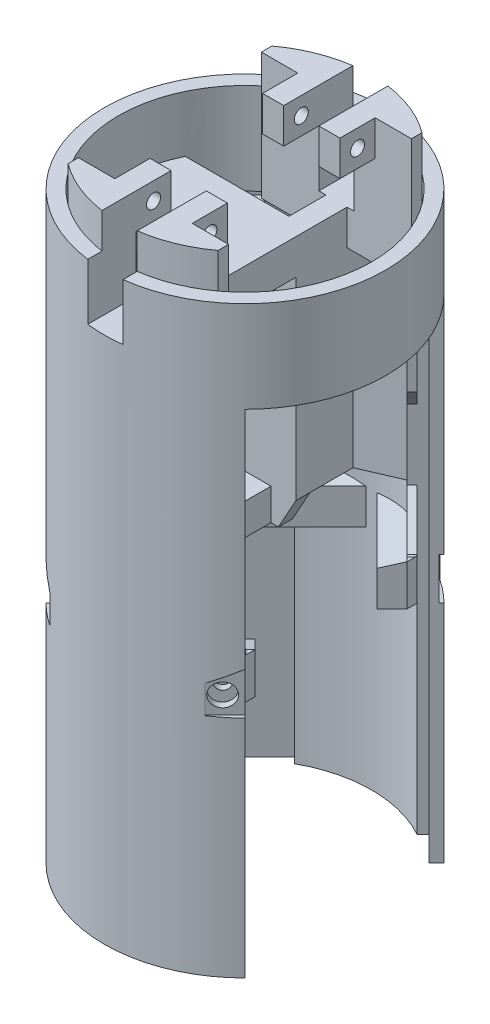
SolidWorks part; units mm, degrees
ref_plane "前视基准面" through (0, 0, 0) normal (0, 0, 1) x (1, 0, 0)
ref_plane "上视基准面" through (0, 0, 0) normal (0, 1, 0) x (1, 0, 0)
ref_plane "右视基准面" through (0, 0, 0) normal (1, 0, 0) x (0, 0, -1)
other "Configuration Table"
sketch "草图1" plane through (0, 0, 0) normal (0, 1, 0) x (1, 0, 0)
  circle A0 centre (0, 0) radius 20
  circle A1 centre (0, 0) radius 18
  dimension "D1" = 40
  dimension "D2" = 36
extrude "凸台-拉伸1" add sketch "草图1" along normal blind 5
sketch "草图2" plane through (0, 0, 0) normal (0, 1, 0) x (1, 0, 0)
  line L0 (0, -1000) -> (0, 49000) construction
  line L2 (-1.5, 17.9374) -> (-1.5, -17.9374)
  line L3 (1.5, 17.9374) -> (1.5, -17.9374)
  arc A0 (-1.5, -17.9374) -> (1.5, -17.9374) centre (0, 0) ccw
  arc A1 (1.5, 17.9374) -> (-1.5, 17.9374) centre (0, 0) ccw
  point P7 (0, 17.9374)
  dimension "D1" = 36
  dimension "D2" = 3
  dimension "D3" = 35.8748
extrude "凸台-拉伸2" add sketch "草图2" along normal blind 5
sketch "草图14" plane through (0, 0, 0) normal (0, 1, 0) x (1, 0, 0)
  line L0 (-1000, 0) -> (49000, 0) construction
  line L1 (0, -1000) -> (0, 49000) construction
  line L2 (-12.4499, 13) -> (12.4499, 13)
  line L3 (-1000, 18) -> (49000, 18) construction
  line L4 (-12.4499, -13) -> (12.4499, -13)
  arc A0 (-12.4499, -13) -> (12.4499, -13) centre (0, 0) ccw
  arc A1 (12.4499, 13) -> (-12.4499, 13) centre (0, 0) ccw
  point P11 (0, 13)
  dimension "D1" = 5
extrude "凸台-拉伸8" add sketch "草图14" along normal up to surface (5 mm away) up to face at (-9.75, 5, 0)
sketch "草图17" plane through (0, 0, 0) normal (0, 1, 0) x (1, 0, 0)
  line L0 (12.4499, 13) -> (2.5, 13)
  line L1 (-1000, 0) -> (49000, 0) construction
  line L12 (-2.5, 13) -> (-12.4499, 13)
  line L26 (-2.5, 17.8255) -> (-2.5, 13)
  line L27 (2.5, 17.8255) -> (2.5, 13)
  line L28 (2.5, -17.8255) -> (2.5, -13)
  line L29 (-2.5, -17.8255) -> (-2.5, -13)
  line L30 (-2.5, -13) -> (-12.4499, -13)
  line L31 (12.4499, -13) -> (2.5, -13)
  arc A0 (-2.5, 17.8255) -> (-12.4499, 13) centre (0, 0) ccw
  arc A1 (12.4499, 13) -> (2.5, 17.8255) centre (0, 0) ccw
  arc A4 (12.4499, -13) -> (2.5, -17.8255) centre (0, 0) cw
  arc A5 (-2.5, -17.8255) -> (-12.4499, -13) centre (0, 0) cw
  dimension "D1" = 4.8255
  dimension "D2" = 5
extrude "凸台-拉伸10" add sketch "草图17" along normal blind 13 from surface starting at face at (8.3625, 5, 0)
sketch "草图25" plane through (0, 0, 0) normal (0, 1, 0) x (1, 0, 0)
  line L1 (1.5, -13) -> (1.5, 13) construction
  line L2 (1.5, -13) -> (1.5, 13) construction
  line L3 (1.5, 7.75) -> (1.5, -7.75)
  line L4 (1.5, -7.75) -> (-16.2462, -7.75)
  line L5 (1.5, 7.75) -> (-16.2462, 7.75)
  arc A0 (-16.2462, 7.75) -> (-16.2462, -7.75) centre (0, 0) ccw
  point P9 (1.5, 0)
  dimension "D1" = 15.5
  dimension "D2" = 17.7462
extrude "凸台-拉伸24" add sketch "草图25" along normal up to surface (5 mm away) from surface up to face at (5.5262, 5, 0) starting at face at (8.3625, 0, 0)
sketch "草图26" plane through (0, 0, 0) normal (0, 1, 0) x (1, 0, 0)
  line L0 (-16.2462, -7.75) -> (1.5, -7.75)
  line L1 (1.5, -13) -> (1.5, 13) construction
  line L2 (1.5, -7.75) -> (1.5, -5.75)
  line L3 (1.5, -5.75) -> (-2.0569, -5.75)
  line L4 (-2.0569, -5.75) -> (-2.0569, 5.75)
  line L5 (-2.0569, 5.75) -> (1.5, 5.75)
  line L6 (1.5, 5.75) -> (1.5, 7.75)
  line L7 (1.5, 7.75) -> (-16.2462, 7.75)
  line L8 (-17.0569, -5.75) -> (-4.0569, -5.75)
  line L9 (-4.0569, -5.75) -> (-4.0569, 5.75)
  line L10 (-4.0569, 5.75) -> (-17.0569, 5.75)
  arc A0 (-16.2462, 7.75) -> (-17.0569, 5.75) centre (0, 0) ccw
  arc A1 (-17.0569, -5.75) -> (-16.2462, -7.75) centre (0, 0) ccw
  dimension "D1" = 2
  dimension "D2" = 2
  dimension "D3" = 2
  dimension "D4" = 13
  dimension "D5" = 11.5
extrude "凸台-拉伸25" add sketch "草图26" against normal blind 32 from surface contours L7 A0 L10 L9 L8 A1 L0 L2 L3 L4 L5 L6 starting at face at (-7.9836, 0, 10.4181)
sketch "草图27" plane through (0, 0, 0) normal (1, 0, 0) x (0, 0, -1)
  line L0 (5.75, 0) -> (-5.75, -32) construction
  line L1 (5.75, -32) -> (-5.75, 0) construction
  line L2 (0, -2.2) -> (0, -29.8) construction
  line L4 (-5.75, -4.5) -> (5.75, -4.5)
  line L5 (-5.75, -4.5) -> (-5.75, -27.5)
  line L6 (-5.75, -27.5) -> (5.75, -27.5)
  line L7 (5.75, -4.5) -> (5.75, -27.5)
  line L8 (-5.75, -4.5) -> (5.75, -27.5) construction
  line L9 (-5.75, -27.5) -> (5.75, -4.5) construction
  circle A0 centre (0, -29.8) radius 1
  circle A1 centre (0, -2.2) radius 1
  point P8 (0, -16)
  point P12 (0, -16)
  point P14 (0, -16)
  dimension "D4" = 2
  dimension "D5" = 2
  dimension "D1" = 27.6
  dimension "D2" = 23
  dimension "D3" = 11.5
extrude "切除-拉伸1" cut sketch "草图27" against normal blind 32
sketch "草图28" plane through (0, 0, 0) normal (0, 0, 1) x (1, 0, 0)
  line L0 (1.5, -32) -> (1.5, -27.5)
  line L1 (1.5, -32) -> (1.5, 0) construction
  line L2 (1.5, -27.5) -> (-1, -32)
  line L3 (1.5, -32) -> (-16.2462, -32) construction
  line L4 (-1, -32) -> (1.5, -32)
  line L5 (-17.0569, -32) -> (-4.0569, -32)
  line L6 (-4.0569, -32) -> (-17.0569, -28.5)
  line L7 (-17.0569, -32) -> (-17.0569, 0) construction
  line L8 (-17.0569, -28.5) -> (-17.0569, -32)
  dimension "D1" = 4.5
  dimension "D2" = 2.5
  dimension "D3" = 3.5
  dimension "D4" = 13
extrude "切除-拉伸2" cut sketch "草图28" against normal through all and the other way blind 32
sketch "草图29" plane through (0, 0, 0) normal (0, 1, 0) x (1, 0, 0)
  line L0 (-17.0569, -5.75) -> (-4.0569, -5.75)
  line L1 (-4.0569, -5.75) -> (-4.0569, -2.75)
  line L2 (-4.0569, 5.75) -> (-4.0569, -5.75) construction
  line L3 (-4.0569, -2.75) -> (-17.7887, -2.75)
  line L4 (-17.0569, 5.75) -> (-4.0569, 5.75)
  line L5 (-4.0569, 5.75) -> (-4.0569, 2.75)
  line L6 (-4.0569, 2.75) -> (-17.7887, 2.75)
  arc A0 (-17.0569, 5.75) -> (-17.7887, 2.75) centre (0, 0) ccw
  arc A1 (-17.7887, -2.75) -> (-17.0569, -5.75) centre (0, 0) ccw
  dimension "D1" = 3
  dimension "D2" = 3
extrude "凸台-拉伸28" add sketch "草图29" along normal blind 1 from surface starting at face at (-3.0569, -4.5, 0)
sketch "草图31" plane through (0, 0, 0) normal (0, 1, 0) x (1, 0, 0)
  line L0 (-17.0569, -5.75) -> (-4.0569, -5.75)
  line L1 (-4.0569, -5.75) -> (-4.0569, -2.75)
  line L2 (-17.0569, 5.75) -> (-4.0569, 5.75)
  line L3 (-4.0569, 5.75) -> (-4.0569, 2.75)
  line L6 (-17.0569, -5.75) -> (-2.0569, -5.75)
  line L7 (-4.0569, -2.75) -> (-17.7887, -2.75)
  line L8 (-4.0569, 2.75) -> (-4.0569, -2.75)
  line L9 (-17.7887, 2.75) -> (-4.0569, 2.75)
  line L10 (-2.0569, 5.75) -> (-17.0569, 5.75)
  line L11 (-2.0569, -5.75) -> (-2.0569, 5.75)
  line L13 (-4.0569, -2.75) -> (-17.7887, -2.75)
  line L15 (-17.7887, 2.75) -> (-4.0569, 2.75)
  arc A2 (-17.7887, -2.75) -> (-17.0569, -5.75) centre (0, 0) ccw
  arc A3 (-17.0569, 5.75) -> (-17.7887, 2.75) centre (0, 0) ccw
  arc A4 (-17.7887, -2.75) -> (-17.0569, -5.75) centre (0, 0) ccw
  arc A5 (-17.0569, 5.75) -> (-17.7887, 2.75) centre (0, 0) ccw
  dimension "D1" = 0
extrude "凸台-拉伸29" add sketch "草图31" against normal blind 1 from surface starting at face at (-3.0569, -27.5, 0)
sketch "草图35" plane through (0, 0, 0) normal (1, 0, 0) x (0, 0, -1)
  line L0 (-8, 18) -> (-13, 13) construction
  line L1 (-13, 18) -> (-8, 18)
  line L2 (-13, 18) -> (-13, 13)
  line L3 (-13, 13) -> (-8, 13)
  line L4 (-8, 18) -> (-8, 13)
  line L5 (13, 18) -> (8, 18)
  line L6 (13, 18) -> (13, 13)
  line L7 (13, 13) -> (8, 13)
  line L8 (8, 18) -> (8, 13)
  line L9 (8, 18) -> (13, 13) construction
  circle A0 centre (10.5, 15.5) radius 1
  circle A1 centre (-10.5, 15.5) radius 1
  dimension "D5" = 2
  dimension "D6" = 2
  dimension "D1" = 5
  dimension "D2" = 5
  dimension "D3" = 5
  dimension "D4" = 5
extrude "凸台-拉伸32" add sketch "草图35" against normal blind 3 from surface starting at face at (-2.5, 11.5, -15.4128)
sketch "草图36" plane through (0, 0, 0) normal (1, 0, 0) x (0, 0, -1)
  line L0 (-13, 13) -> (-13, 18) construction
  line L1 (-13, 18) -> (-8, 18) construction
  line L2 (-8, 18) -> (-8, 13) construction
  line L3 (-8, 13) -> (-13, 13) construction
  line L4 (13, 18) -> (13, 13) construction
  line L5 (13, 13) -> (8, 13) construction
  line L6 (8, 13) -> (8, 18) construction
  line L7 (8, 18) -> (13, 18) construction
  line L8 (-13, 13) -> (-13, 18)
  line L9 (-13, 18) -> (-8, 18)
  line L10 (-8, 18) -> (-8, 13)
  line L11 (-8, 13) -> (-13, 13)
  line L12 (13, 18) -> (13, 13)
  line L13 (13, 13) -> (8, 13)
  line L14 (8, 13) -> (8, 18)
  line L15 (8, 18) -> (13, 18)
  circle A0 centre (-10.5, 15.5) radius 1 construction
  circle A1 centre (-10.5, 15.5) radius 1
  circle A2 centre (10.5, 15.5) radius 1 construction
  circle A3 centre (10.5, 15.5) radius 1
extrude "凸台-拉伸33" add sketch "草图36" along normal blind 3 from surface starting at face at (2.5, 11.5, 15.4128)
sketch "草图37" plane through (0, 0, 0) normal (0, 1, 0) x (1, 0, 0)
  line L0 (2.5, 13) -> (2.5, 17.8255) construction
  line L1 (2.5, -19.8431) -> (2.5, -17.8255)
  line L2 (-2.5, 17.8255) -> (-2.5, 8) construction
  line L3 (-2.5, 19.8431) -> (-2.5, 17.8255)
  line L4 (2.5, 17.8255) -> (2.5, 19.8431)
  line L5 (-2.5, -17.8255) -> (-2.5, -19.8431)
  arc A0 (-2.5, 17.8255) -> (-2.5, -17.8255) centre (0, 0) ccw
  arc A1 (-2.5, 19.8431) -> (-2.5, -19.8431) centre (0, 0) ccw
  arc A2 (2.5, -17.8255) -> (2.5, 17.8255) centre (0, 0) ccw
  arc A3 (2.5, -19.8431) -> (2.5, 19.8431) centre (0, 0) ccw
  dimension "D1" = 40
extrude "凸台-拉伸35" add sketch "草图37" along normal blind 8 from surface starting at face at (5.5262, 5, 0)
sketch "草图38" plane through (0, 0, 0) normal (0, 1, 0) x (1, 0, 0)
  circle A0 centre (0, 0) radius 20
  circle A1 centre (0, 0) radius 18
  dimension "D1" = 40
extrude "凸台-拉伸36" add sketch "草图38" against normal blind 70
sketch "草图39" plane through (0, 0, 0) normal (0, 1, 0) x (1, 0, 0)
  line L0 (-707.1068, -707.1068) -> (34648.2323, 34648.2323) construction
  line L1 (707.1068, -707.1068) -> (-34648.2323, 34648.2323) construction
  line L2 (14.1421, -14.1421) -> (12.7279, -12.7279)
  line L3 (-14.1421, -14.1421) -> (-12.7279, -12.7279)
  line L4 (-12.7279, 12.7279) -> (-14.1421, 14.1421)
  line L5 (14.1421, 14.1421) -> (12.7279, 12.7279)
  arc A0 (14.1421, -14.1421) -> (14.1421, 14.1421) centre (0, 0) ccw
  arc A1 (12.7279, -12.7279) -> (12.7279, 12.7279) centre (0, 0) ccw
  arc A2 (-14.1421, 14.1421) -> (-14.1421, -14.1421) centre (0, 0) ccw
  arc A3 (-12.7279, 12.7279) -> (-12.7279, -12.7279) centre (0, 0) ccw
  dimension "D1" = 40
extrude "切除-拉伸3" cut sketch "草图39" along normal up to surface (70 mm away) from surface up to face at (-0.2784, 0, 0) starting at face at (0, -70, 18)
sketch "草图40" plane through (0, 0, 0) normal (0, 1, 0) x (1, 0, 0)
  line L0 (1.5, -7.75) -> (1.5, -17.9374)
  line L1 (-1.5, -17.9374) -> (-1.5, -7.75)
  line L2 (1.5, 7.75) -> (1.5, 17.9374)
  line L3 (-1.5, 7.75) -> (-1.5, 17.9374)
  line L5 (1.5, 13) -> (12.4499, 13)
  line L6 (1.5, 7.75) -> (1.5, 13)
  line L7 (-1.5, 7.75) -> (1.5, 7.75)
  line L8 (-1.5, 13) -> (-1.5, 7.75)
  line L9 (-12.4499, 13) -> (-1.5, 13)
  line L11 (1.5, 7.75) -> (1.5, 13)
  line L12 (-1.5, 7.75) -> (1.5, 7.75)
  line L13 (-1.5, 13) -> (-1.5, 7.75)
  line L15 (-1.5, -13) -> (-12.4499, -13)
  line L16 (-1.5, -7.75) -> (-1.5, -13)
  line L17 (1.5, -7.75) -> (-1.5, -7.75)
  line L18 (1.5, -13) -> (1.5, -7.75)
  line L19 (12.4499, -13) -> (1.5, -13)
  line L21 (-1.5, -7.75) -> (-1.5, -13)
  line L22 (1.5, -7.75) -> (-1.5, -7.75)
  line L23 (1.5, -13) -> (1.5, -7.75)
  arc A1 (12.4499, 13) -> (-12.4499, 13) centre (0, 0) ccw
  arc A2 (1.5, 17.9374) -> (-1.5, 17.9374) centre (0, 0) ccw
  arc A3 (-12.4499, -13) -> (12.4499, -13) centre (0, 0) ccw
  arc A4 (-1.5, -17.9374) -> (1.5, -17.9374) centre (0, 0) ccw
  dimension "D1" = 0
  dimension "D2" = 0
extrude "凸台-拉伸37" add sketch "草图40" against normal up to vertex from surface contours L1 A4 L0 L22 | L2 A2 L3 L12 region at (0, 0, 12.8646) region at (0, 0, -12.8646) up to point (1.5, -27.5, 7.75) starting at face at (-0.2784, 0, 0)
sketch "草图41" plane through (0, 0, 0) normal (0, 1, 0) x (1, 0, 0)
  line L0 (-1000, 0) -> (49000, 0) construction
  line L1 (0, -1000) -> (0, 49000) construction
  line L2 (-707.1068, -707.1068) -> (34648.2323, 34648.2323) construction
  line L3 (707.1068, -707.1068) -> (-34648.2323, 34648.2323) construction
  line L4 (-15.7626, -8.6915) -> (-8.6915, -15.7626)
  line L5 (16.6111, -9.54) -> (9.54, -16.6111)
  line L6 (-16.6111, -9.54) -> (-9.54, -16.6111)
  line L7 (-9.54, -16.6111) -> (-8.6915, -15.7626)
  line L8 (-16.6111, -9.54) -> (-15.7626, -8.6915)
  line L9 (9.54, -16.6111) -> (8.6915, -15.7626)
  line L10 (15.7626, -8.6915) -> (8.6915, -15.7626)
  line L11 (16.6111, -9.54) -> (15.7626, -8.6915)
  line L12 (16.6111, 9.54) -> (15.7626, 8.6915)
  line L13 (15.7626, 8.6915) -> (8.6915, 15.7626)
  line L14 (9.54, 16.6111) -> (8.6915, 15.7626)
  line L15 (16.6111, 9.54) -> (9.54, 16.6111)
  line L16 (-16.6111, 9.54) -> (-9.54, 16.6111)
  line L17 (-9.54, 16.6111) -> (-8.6915, 15.7626)
  line L18 (-15.7626, 8.6915) -> (-8.6915, 15.7626)
  line L19 (-16.6111, 9.54) -> (-15.7626, 8.6915)
  circle A0 centre (0, 0) radius 18 construction
  point P15 (-12.227, -12.227)
  point P21 (-13.0755, -13.0755)
  dimension "D1" = 10
  dimension "D3" = 10
  dimension "D4" = 1.2
extrude "切除-拉伸4" cut sketch "草图41" against normal up to surface (70 mm away) from surface up to face at (0, -70, 16.2175) starting at face at (-0.2784, 0, 0)
sketch "草图42" plane through (0, 0, 0) normal (0, 1, 0) x (1, 0, 0)
  line L0 (-1000, 0) -> (49000, 0) construction
  line L1 (0, -1000) -> (0, 49000) construction
  line L2 (-707.1068, -707.1068) -> (34648.2323, 34648.2323) construction
  line L3 (707.1068, -707.1068) -> (-34648.2323, 34648.2323) construction
  line L4 (-12.227, -12.227) -> (-8.6915, -15.7626)
  line L5 (-11.5199, -11.5199) -> (-6.1077, -16.9321)
  line L6 (-11.5199, -11.5199) -> (-12.227, -12.227)
  line L7 (11.5199, -11.5199) -> (12.227, -12.227)
  line L8 (12.227, -12.227) -> (8.6915, -15.7626)
  line L9 (11.5199, -11.5199) -> (6.1077, -16.9321)
  line L10 (-11.5199, 11.5199) -> (-12.227, 12.227)
  line L11 (-12.227, 12.227) -> (-8.6915, 15.7626)
  line L12 (-11.5199, 11.5199) -> (-6.1077, 16.9321)
  line L13 (11.5199, 11.5199) -> (12.227, 12.227)
  line L14 (12.227, 12.227) -> (8.6915, 15.7626)
  line L15 (11.5199, 11.5199) -> (6.1077, 16.9321)
  arc A0 (-8.6915, -15.7626) -> (-6.1077, -16.9321) centre (0, 0) ccw
  arc A1 (8.6915, -15.7626) -> (6.1077, -16.9321) centre (0, 0) cw
  arc A2 (-8.6915, 15.7626) -> (-6.1077, 16.9321) centre (0, 0) cw
  arc A3 (8.6915, 15.7626) -> (6.1077, 16.9321) centre (0, 0) ccw
  point P15 (-12.227, -12.227)
  point P18 (-11.5199, -11.5199)
  dimension "D1" = 1
extrude "凸台-拉伸39" add sketch "草图42" against normal blind 38 from surface starting at face at (-0.2784, 0, 0)
ref_plane "45度面" through (0, 0, 0) normal (-0.7071, 0, 0.7071) x (0, -1, 0)
sketch "草图44" plane through (0, 0, 0) normal (-0.7071, 0, 0.7071) x (0, -1, 0)
  line L0 (-962, -5) -> (49038, -5) construction
  line L1 (27, -5) -> (17, -5)
  line L3 (27, -5) -> (27, -3) construction
  line L4 (27, -5) -> (32, 0)
  line L5 (38, 0) -> (0, 0) construction
  line L6 (17, -5) -> (17, -3) construction
  line L8 (17, -5) -> (12, 0)
  line L9 (12, 0) -> (32, 0)
  line L10 (0, -20) -> (0, 0) construction
  point P6 (22, -5)
  dimension "D1" = 22
  dimension "D2" = 2
  dimension "D3" = 10
  dimension "D4" = 45
  dimension "D5" = 2
  dimension "D6" = 45
extrude "切除-拉伸5" cut sketch "草图44" against normal up to next from surface starting at face at (9.059, -15.2, -13.9808)
ref_plane "135度面" through (0, 0, 0) normal (-0.7071, 0, -0.7071) x (0, -1, 0)
sketch "草图45" plane through (0, 0, 0) normal (-0.7071, 0, -0.7071) x (0, -1, 0)
  line L0 (70, 5) -> (38, 5) construction
  line L1 (70, 5) -> (38, 5) construction
  line L2 (17, 5) -> (27, 5)
  line L3 (0, -18) -> (0, 0.389) construction
  line L4 (27, 5) -> (27, 3) construction
  line L5 (17, 5) -> (17, 3) construction
  line L7 (27, 5) -> (32, 0)
  line L8 (38, 0) -> (0, 0) construction
  line L9 (32, 0) -> (12, 0)
  line L10 (12, 0) -> (17, 5)
  point P7 (22, 5)
  dimension "D1" = 10
  dimension "D2" = 22
  dimension "D3" = 2
  dimension "D4" = 2
  dimension "D5" = 45
  dimension "D6" = 45
extrude "切除-拉伸6" cut sketch "草图45" against normal up to next from surface starting at face at (9.059, -15.2, 13.9808)
sketch "草图47" plane through (0, 0, 0) normal (-0.7071, 0, 0.7071) x (0, -1, 0)
  line L0 (0, 0) -> (70, 0) construction
  line L1 (0, 0) -> (70, 0) construction
  line L10 (38, 0) -> (38, 4)
  line L12 (38, 0) -> (32, 0)
  line L13 (32, 0) -> (34, 4)
  line L14 (38, 4) -> (34, 4)
  dimension "D1" = 4
  dimension "D2" = 4
extrude "切除-拉伸7" cut sketch "草图47" along normal up to next from offset 19.5
sketch "草图49" plane through (0, 0, 0) normal (-0.7071, 0, 0.7071) x (0, -1, 0)
  line L0 (0, 0) -> (38, 0) construction
  line L1 (0, 0) -> (70, 0) construction
  line L2 (38, 0) -> (38, 7.654) construction
  line L3 (38, 0) -> (38, -4)
  line L4 (38, -4) -> (34, -4)
  line L5 (34, -4) -> (32, 0)
  line L6 (32, -5.5203) -> (32, 2.6114) construction
  line L7 (32, 0) -> (38, 0)
  dimension "D1" = 4
  dimension "D2" = 4
extrude "切除-拉伸8" cut sketch "草图49" against normal up to next from offset 19.5 contours L7 L3 L4 L5 offset against normal yes
sketch "草图50" plane through (0, 0, 0) normal (-0.7071, 0, -0.7071) x (0, -1, 0)
  line L0 (0, 0) -> (38, 0) construction
  line L1 (38, -4) -> (34, -4)
  line L2 (34, -4) -> (32, 0)
  line L3 (38, 0) -> (38, -4)
  line L4 (38, 0) -> (32, 0)
  dimension "D1" = 4
  dimension "D2" = 4
extrude "切除-拉伸9" cut sketch "草图50" along normal up to next from offset 19.5 contours L4 L2 L1 L3
sketch "草图51" plane through (0, 0, 0) normal (-0.7071, 0, -0.7071) x (0, -1, 0)
  line L0 (0, 0) -> (38, 0) construction
  line L1 (38, 0) -> (38, 4)
  line L2 (38, 4) -> (34, 4)
  line L3 (34, 4) -> (31.9993, 0)
  line L4 (31.9993, 0) -> (38, 0)
  dimension "D1" = 4
  dimension "D2" = 4
  dimension "D3" = 6.0007
extrude "切除-拉伸10" cut sketch "草图51" against normal up to next from offset 19.5 offset against normal yes
sketch "草图53" plane through (0, 0, 0) normal (-0.7071, 0, 0.7071) x (0, -1, 0)
  line L0 (0, 0) -> (38, 0) construction
  line L1 (38, 0) -> (38, 4) construction
  circle A0 centre (35.5, 2.25) radius 1.6
  dimension "D1" = 3.2
  dimension "D2" = 2.25
  dimension "D3" = 2.5
extrude "切除-拉伸11" cut sketch "草图53" along normal through all from surface starting at face at (-11.3078, -35, 14.8433)
sketch "草图54" plane through (0, 0, 0) normal (-0.7071, 0, 0.7071) x (0, -1, 0)
  line L0 (38, 0) -> (0, 0) construction
  line L1 (38, 0) -> (38, -4) construction
  circle A0 centre (35.5, -2.225) radius 1.6
  dimension "D3" = 3.2
  dimension "D1" = 2.225
  dimension "D2" = 2.5
extrude "切除-拉伸12" cut sketch "草图54" against normal up to next from surface starting at face at (11.3078, -35, -14.8433)
sketch "草图55" plane through (0, 0, 0) normal (-0.7071, 0, -0.7071) x (0, -1, 0)
  line L0 (38, 0) -> (32, 0) construction
  line L1 (38, 0) -> (38, -4) construction
  circle A0 centre (35.5, -2.25) radius 1.6
  dimension "D1" = 3.2
  dimension "D2" = 2.25
  dimension "D3" = 2.5
extrude "切除-拉伸13" cut sketch "草图55" along normal up to next from surface starting at face at (-11.3078, -35, -14.8433)
sketch "草图56" plane through (0, 0, 0) normal (-0.7071, 0, -0.7071) x (0, -1, 0)
  line L0 (38, 4) -> (38, 0) construction
  line L1 (31.9993, 0) -> (38, 0) construction
  circle A0 centre (35.5, 2.25) radius 1.6
  dimension "D1" = 3.2
  dimension "D2" = 2.5
  dimension "D3" = 2.25
extrude "切除-拉伸14" cut sketch "草图56" against normal up to next from surface contours A0 starting at face at (11.3078, -35, 14.8433)
sketch "草图61" plane through (0, 0, 0) normal (-0.7071, 0, 0.7071) x (0, -1, 0)
  line L0 (33, -13.2916) -> (32.1962, -16.2916)
  line L1 (38, -16.2916) -> (33, -16.2916)
  line L2 (38, -16.2916) -> (38, -13.2916)
  line L3 (38, -13.2916) -> (33, -13.2916)
  line L4 (33, -16.2916) -> (33, -13.2916) construction
  line L5 (32.1962, -16.2916) -> (33, -16.2916)
  dimension "D1" = 3
  dimension "D2" = 5
  dimension "D3" = 15
extrude "凸台-拉伸40" add sketch "草图61" against normal up to next and the other way blind 1 from surface starting at face at (-11.8735, -19, -11.8735)
sketch "草图62" plane through (0, 0, 0) normal (-0.7071, 0, 0.7071) x (0, -1, 0)
  line L0 (33, 13.2916) -> (32.1962, 16.2916)
  line L1 (38, 16.2916) -> (33, 16.2916)
  line L2 (38, 16.2916) -> (38, 13.2916)
  line L3 (38, 13.2916) -> (33, 13.2916)
  line L4 (33, 16.2916) -> (33, 13.2916) construction
  line L5 (38, 16.2916) -> (0, 16.2916) construction
  line L6 (32.1962, 16.2916) -> (33, 16.2916)
  dimension "D1" = 3
  dimension "D2" = 5
  dimension "D3" = 15
extrude "凸台-拉伸41" add sketch "草图62" along normal up to next and the other way blind 1
sketch "草图63" plane through (0, 0, 0) normal (-0.7071, 0, -0.7071) x (0, -1, 0)
  line L0 (38, 16.2916) -> (0, 16.2916) construction
  line L1 (38, 16.2916) -> (33, 16.2916)
  line L2 (38, 16.2916) -> (38, 13.2916)
  line L3 (38, 13.2916) -> (33, 13.2916)
  line L4 (33, 16.2916) -> (33, 13.2916) construction
  line L5 (38, 16.2916) -> (0, 16.2916) construction
  line L6 (33, 13.2916) -> (32.1962, 16.2916)
  line L7 (32.1962, 16.2916) -> (33, 16.2916)
  dimension "D1" = 3
  dimension "D2" = 5
  dimension "D3" = 15
extrude "凸台-拉伸42" add sketch "草图63" against normal up to next and the other way blind 1
sketch "草图64" plane through (0, 0, 0) normal (-0.7071, 0, -0.7071) x (0, -1, 0)
  line L0 (33, -13.2916) -> (32.1962, -16.2916)
  line L1 (38, -16.2916) -> (33, -16.2916)
  line L2 (38, -16.2916) -> (38, -13.2916)
  line L3 (38, -13.2916) -> (33, -13.2916)
  line L4 (33, -16.2916) -> (33, -13.2916) construction
  line L5 (38, -16.2916) -> (0, -16.2916) construction
  line L6 (32.1962, -16.2916) -> (33, -16.2916)
  dimension "D1" = 3
  dimension "D2" = 5
  dimension "D3" = 15
extrude "凸台-拉伸43" add sketch "草图64" along normal up to next and the other way blind 1
sketch "草图67" plane through (0, 0, 0) normal (0, 1, 0) x (1, 0, 0)
  line L0 (7.3833, 13.3937) -> (10.2118, 10.5653)
  line L1 (10.2118, 10.5653) -> (11.3431, 11.6967)
  line L2 (11.3431, 11.6967) -> (8.5147, 14.5251)
  line L3 (8.5147, 14.5251) -> (7.3833, 13.3937)
  line L4 (8.6915, 15.7626) -> (12.227, 12.227) construction
  line L7 (-1000, 0) -> (49000, 0) construction
  line L8 (0, -1000) -> (0, 49000) construction
  line L9 (8.5147, -14.5251) -> (7.3833, -13.3937)
  line L10 (11.3431, -11.6967) -> (8.5147, -14.5251)
  line L11 (10.2118, -10.5653) -> (11.3431, -11.6967)
  line L12 (7.3833, -13.3937) -> (10.2118, -10.5653)
  line L13 (-7.3833, -13.3937) -> (-10.2118, -10.5653)
  line L14 (-10.2118, -10.5653) -> (-11.3431, -11.6967)
  line L15 (-11.3431, -11.6967) -> (-8.5147, -14.5251)
  line L16 (-8.5147, -14.5251) -> (-7.3833, -13.3937)
  line L17 (-8.5147, 14.5251) -> (-7.3833, 13.3937)
  line L18 (-11.3431, 11.6967) -> (-8.5147, 14.5251)
  line L19 (-10.2118, 10.5653) -> (-11.3431, 11.6967)
  line L20 (-7.3833, 13.3937) -> (-10.2118, 10.5653)
  line L23 (12.227, 12.227) -> (11.5199, 11.5199) construction
  dimension "D1" = 1.6
  dimension "D2" = 4
  dimension "D3" = 1
  dimension "D4" = 4.25
extrude "切除-拉伸25" cut sketch "草图67" along normal blind 3.65 from surface starting at face at (9.2858, -38, -12.9081)
sketch "草图71" plane through (0, 0, 0) normal (0, 1, 0) x (1, 0, 0)
  line L0 (12.227, -12.227) -> (12.227, -10.8128)
  line L1 (12.227, -10.8128) -> (11.5199, -11.5199)
  line L2 (11.5199, -11.5199) -> (12.227, -12.227)
  line L3 (11.5199, 11.5199) -> (12.227, 12.227)
  line L4 (12.227, 12.227) -> (12.227, 10.8128)
  line L5 (12.227, 10.8128) -> (11.5199, 11.5199)
  line L6 (-12.227, 12.227) -> (-11.5199, 11.5199)
  line L7 (-11.5199, 11.5199) -> (-12.227, 10.8128)
  line L8 (-12.227, 10.8128) -> (-11.5199, 11.5199) construction
  line L9 (-12.227, 10.8128) -> (-12.227, 12.227)
  line L10 (-12.227, -12.227) -> (-12.227, -10.8128)
  line L11 (-12.227, -10.8128) -> (-11.5199, -11.5199)
  line L12 (-12.227, -10.8128) -> (-11.5199, -11.5199) construction
  line L13 (-12.227, -12.227) -> (-11.5199, -11.5199) construction
  line L14 (-11.5199, -11.5199) -> (-12.227, -12.227)
extrude "凸台-拉伸45" add sketch "草图71" along normal up to vertex from surface up to point (-12.227, -32.1962, 10.8128) starting at face at (-9.2858, -38, 12.9081)
fillet "圆角7" radius 0.2 2 edges at (11.8735, -32.1962, 11.8735) (11.8735, -32.1962, -11.8735)
sketch "草图78" plane through (0, 0, 0) normal (-0.7071, 0, -0.7071) x (0, -1, 0)
  circle A0 centre (35.5, 2.25) radius 1
  dimension "D1" = 2
extrude "切除-拉伸34" cut sketch "草图78" against normal through all
sketch "草图80" plane through (0, 0, 0) normal (-0.7071, 0, 0.7071) x (0, -1, 0)
  circle A0 centre (35.5, 2.25) radius 1
  dimension "D1" = 2
extrude "切除-拉伸36" cut sketch "草图80" along normal through all
sketch "草图81" plane through (0, 0, 0) normal (-0.7071, 0, 0.7071) x (0, -1, 0)
  circle A0 centre (35.5, -2.225) radius 1
  dimension "D1" = 2
extrude "切除-拉伸37" cut sketch "草图81" against normal through all
sketch "草图82" plane through (0, 0, 0) normal (-0.7071, 0, -0.7071) x (0, -1, 0)
  circle A0 centre (35.5, -2.25) radius 1
  dimension "D1" = 2
extrude "切除-拉伸38" cut sketch "草图82" along normal through all
sketch "草图83" plane through (0, 0, 0) normal (-0.7071, 0, 0.7071) x (0, -1, 0)
  line L1 (37.8094, 2.25) -> (36.6547, 4.25)
  line L2 (36.6547, 4.25) -> (34.3453, 4.25)
  line L3 (34.3453, 4.25) -> (33.1906, 2.25)
  line L4 (33.1906, 2.25) -> (34.3453, 0.25)
  line L5 (34.3453, 0.25) -> (36.6547, 0.25)
  line L6 (36.6547, 0.25) -> (37.8094, 2.25)
  circle A0 centre (35.5, 2.25) radius 2 construction
  dimension "D1" = 4
extrude "切除-拉伸39" cut sketch "草图83" against normal blind 1.6 from surface starting at face at (-10.636, -35.5, 12.4038)
sketch "草图84" plane through (0, 0, 0) normal (-0.7071, 0, 0.7071) x (0, -1, 0)
  line L1 (34.3453, -4.225) -> (36.6547, -4.225)
  line L2 (36.6547, -4.225) -> (37.8094, -2.225)
  line L3 (37.8094, -2.225) -> (36.6547, -0.225)
  line L4 (36.6547, -0.225) -> (34.3453, -0.225)
  line L5 (34.3453, -0.225) -> (33.1906, -2.225)
  line L6 (33.1906, -2.225) -> (34.3453, -4.225)
  circle A0 centre (35.5, -2.225) radius 2 construction
  dimension "D1" = 4
extrude "切除-拉伸40" cut sketch "草图84" along normal blind 1.6 from surface starting at face at (10.6537, -35.5, -12.3861)
sketch "草图85" plane through (0, 0, 0) normal (-0.7071, 0, -0.7071) x (0, -1, 0)
  line L1 (37.8094, -2.25) -> (36.6547, -0.25)
  line L2 (36.6547, -0.25) -> (34.3453, -0.25)
  line L3 (34.3453, -0.25) -> (33.1906, -2.25)
  line L4 (33.1906, -2.25) -> (34.3453, -4.25)
  line L5 (34.3453, -4.25) -> (36.6547, -4.25)
  line L6 (36.6547, -4.25) -> (37.8094, -2.25)
  circle A0 centre (35.5, -2.25) radius 2 construction
  point P1 (35.5, -0.25)
  dimension "D1" = 4
extrude "切除-拉伸41" cut sketch "草图85" against normal blind 1.6 from surface starting at face at (-9.2218, -35.5, -13.818)
sketch "草图86" plane through (0, 0, 0) normal (-0.7071, 0, -0.7071) x (0, -1, 0)
  line L1 (33.1906, 2.25) -> (34.3453, 0.25)
  line L2 (34.3453, 0.25) -> (36.6547, 0.25)
  line L3 (36.6547, 0.25) -> (37.8094, 2.25)
  line L4 (37.8094, 2.25) -> (36.6547, 4.25)
  line L5 (36.6547, 4.25) -> (34.3453, 4.25)
  line L6 (34.3453, 4.25) -> (33.1906, 2.25)
  circle A0 centre (35.5, 2.25) radius 2 construction
  dimension "D1" = 4
extrude "切除-拉伸42" cut sketch "草图86" along normal blind 1.6 from surface starting at face at (9.2218, -35.5, 13.818)
sketch "草图87" plane through (0, 0, 0) normal (0, 1, 0) x (1, 0, 0)
  line L3 (-5.5, -13) -> (-12.4499, -13) construction
  line L5 (12.4499, -13) -> (5.5, -13) construction
  line L11 (5.5, 13) -> (12.4499, 13) construction
  line L13 (-12.4499, 13) -> (-5.5, 13) construction
  line L19 (-10.6654, -13) -> (-12.4499, -13)
  line L21 (12.4499, -13) -> (10.6654, -13)
  line L27 (10.6654, 13) -> (12.4499, 13)
  line L29 (-12.4499, 13) -> (-10.6654, 13)
  line L32 (10.6654, 13) -> (10.6654, 14.5)
  line L33 (10.6654, -13) -> (10.6654, -14.5)
  line L34 (-10.6654, -13) -> (-10.6654, -14.5)
  line L35 (-10.6654, 14.5) -> (-10.6654, 13)
  arc A0 (-12.4499, -13) -> (-2.5, -17.8255) centre (0, 0) ccw construction
  arc A1 (2.5, -17.8255) -> (12.4499, -13) centre (0, 0) ccw construction
  arc A2 (12.4499, 13) -> (2.5, 17.8255) centre (0, 0) ccw construction
  arc A3 (-2.5, 17.8255) -> (-12.4499, 13) centre (0, 0) ccw construction
  arc A4 (-12.4499, -13) -> (-10.6654, -14.5) centre (0, 0) ccw
  arc A5 (10.6654, -14.5) -> (12.4499, -13) centre (0, 0) ccw
  arc A6 (12.4499, 13) -> (10.6654, 14.5) centre (0, 0) ccw
  arc A7 (-10.6654, 14.5) -> (-12.4499, 13) centre (0, 0) ccw
  dimension "D1" = 1.5
  dimension "D2" = 1.5
  dimension "D3" = 1.5
extrude "切除-拉伸43" cut sketch "草图87" against normal up to surface from surface up to face at (-4.7952, 0, 15.2553) starting at face at (-5.7659, 18, -12.1217)
sketch "草图88" plane through (0, 0, 0) normal (0, 1, 0) x (1, 0, 0)
  line L0 (1.5, 17.9374) -> (1.5, 14.9374) construction
  line L1 (1.5, 17.9374) -> (1.5, 7.75) construction
  line L2 (1.5, 14.9374) -> (6.1077, 16.9321)
  line L3 (-1.5, 14.9374) -> (-6.1077, 16.9321)
  line L4 (-1.5, 17.9374) -> (-1.5, 7.75) construction
  line L5 (-1.5, 14.9374) -> (-1.5, 17.9374) construction
  line L6 (1.5, -17.9374) -> (1.5, -14.9374) construction
  line L7 (1.5, -17.9374) -> (1.5, -7.75) construction
  line L8 (-1.5, -14.9374) -> (-6.1077, -16.9321)
  line L9 (-1.5, -14.9374) -> (-1.5, -17.9374) construction
  line L10 (-1.5, -7.75) -> (-1.5, -17.9374) construction
  line L11 (1.5, -14.9374) -> (6.1077, -16.9321)
  line L12 (6.8682, -16.1716) -> (1.5, -13.8477)
  line L13 (11.6613, -11.3785) -> (6.1077, -16.9321) construction
  line L14 (1.5, -13.8477) -> (1.5, -14.9374)
  line L15 (6.8682, -16.1716) -> (6.1077, -16.9321)
  line L16 (1.5, -13.8477) -> (1.5, -14.9374)
  line L17 (-1.5, -13.8477) -> (-6.8682, -16.1716)
  line L18 (-11.5199, -11.5199) -> (-6.1077, -16.9321) construction
  line L19 (-6.8682, -16.1716) -> (-6.1077, -16.9321)
  line L20 (-1.5, -13.8477) -> (-1.5, -14.9374)
  line L21 (6.8682, 16.1716) -> (1.5, 13.8477)
  line L22 (11.6613, 11.3785) -> (6.1077, 16.9321) construction
  line L23 (6.8682, 16.1716) -> (6.1077, 16.9321)
  line L24 (1.5, 14.9374) -> (1.5, 13.8477)
  line L25 (-1.5, 13.8477) -> (-6.941, 16.2031)
  line L26 (-1.5, 14.9374) -> (-1.5, 13.8477)
  line L27 (-6.1077, 16.9321) -> (-6.8682, 16.1716)
  line L28 (-11.5199, 11.5199) -> (-6.1077, 16.9321) construction
  arc A0 (0.8157, -17.9815) -> (6.1077, -16.9321) centre (0, 0) ccw construction
  arc A1 (-6.1077, -16.9321) -> (-0.8157, -17.9815) centre (0, 0) ccw construction
  arc A2 (6.1077, 16.9321) -> (0.8157, 17.9815) centre (0, 0) ccw construction
  arc A3 (-0.8157, 17.9815) -> (-6.1077, 16.9321) centre (0, 0) ccw construction
  arc A4 (0.8157, -17.9815) -> (6.1077, -16.9321) centre (0, 0) ccw construction
  arc A5 (-6.1077, -16.9321) -> (-0.8157, -17.9815) centre (0, 0) ccw construction
  arc A6 (6.1077, 16.9321) -> (0.8157, 17.9815) centre (0, 0) ccw construction
  arc A7 (-0.8157, 17.9815) -> (-6.1077, 16.9321) centre (0, 0) ccw construction
  dimension "D7" = 1
  dimension "D1" = 3
  dimension "D2" = 3
  dimension "D3" = 3
  dimension "D4" = 3
  dimension "D5" = 1
  dimension "D6" = 1
  dimension "D8" = 1
extrude "凸台-拉伸46" add sketch "草图88" along normal blind 15 from surface contours L2 L24 L21 L23 | L3 L27 L25 L26 | L15 L12 L14 L11 | L20 L17 L19 L8 region at (3.9988, 0, -15.4604) region at (-3.9988, 0, -15.4604) region at (-3.9988, 0, 15.4604) region at (3.9988, 0, 15.4604) starting at face at (0, -27.5, -12.8593)
